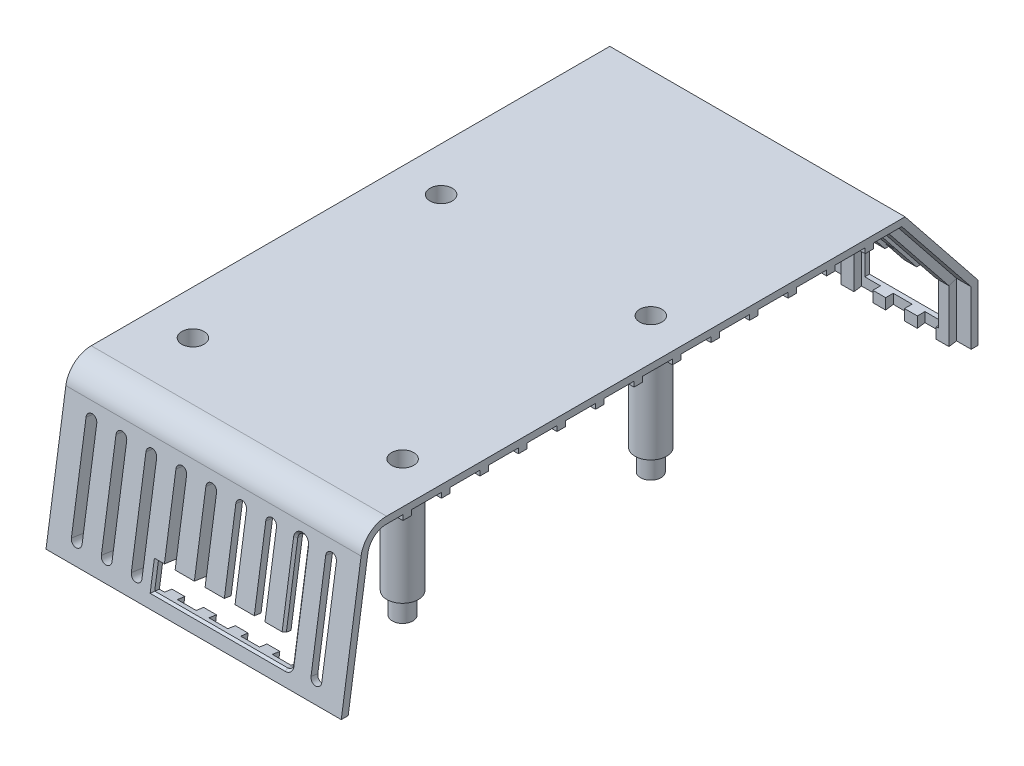
SolidWorks part; units mm, degrees
material "PPS"
ref_plane "前视基准面" through (0, 0, 0) normal (0, 0, 1) x (1, 0, 0)
ref_plane "上视基准面" through (0, 0, 0) normal (0, 1, 0) x (1, 0, 0)
ref_plane "右视基准面" through (0, 0, 0) normal (1, 0, 0) x (0, 0, -1)
sketch "草图2" plane through (0, 0, 0) normal (1, 0, 0) x (0, 0, -1)
  line L32 (-2.0016, 4.5) -> (-2.0016, 17.1644)
  line L33 (-2.0016, 17.1644) -> (-18.214, 37.4471)
  line L34 (-18.214, 37.4471) -> (-138.6289, 37.4471)
  line L35 (-142.9799, 33.7021) -> (-147.3763, 4.5)
  line L36 (0, 0) -> (-169.6172, 0) construction
  line L38 (-17.4446, 39.0471) -> (-138.6289, 39.0471)
  line L39 (-144.5621, 33.9403) -> (-148.9943, 4.5)
  line L40 (-0.4016, 4.5) -> (-0.4016, 17.7253)
  line L41 (-0.4016, 17.7253) -> (-17.4446, 39.0471)
  line L42 (-147.3763, 4.5) -> (-148.9943, 4.5) construction
  line L43 (-142.9799, 33.7021) -> (-147.9563, 0.6471) construction
  line L44 (-147.9563, 0.6471) -> (-2.0016, 0.6471) construction
  line L45 (-149.8153, -0.9529) -> (-0.4016, -0.9529) construction
  line L46 (-144.5621, 33.9403) -> (-149.8153, -0.9529) construction
  line L47 (-0.4016, -0.9529) -> (-0.4016, 17.7253) construction
  line L48 (-2.0016, 0.6471) -> (-2.0016, 17.1644) construction
  line L49 (-2.0016, 4.5) -> (-0.4016, 4.5)
  line L50 (-148.9943, 4.5) -> (-149.1976, 3.15)
  line L51 (-149.1976, 3.15) -> (-147.5795, 3.15)
  line L52 (-147.5795, 3.15) -> (-147.3763, 4.5)
  arc A4 (-138.6289, 39.0471) -> (-144.5621, 33.9403) centre (-138.6289, 33.0471) ccw
  arc A5 (-138.6289, 37.4471) -> (-142.9799, 33.7021) centre (-138.6289, 33.0471) ccw
  dimension "D1" = 1.6
  dimension "D3" = 6
  dimension "D2" = 4.5
  dimension "D4" = 3.15
extrude "凸台-拉伸1" add sketch "草图2" along normal blind 69
sketch "草图7" plane through (0, 3.15, 0) normal (0, -1, 0) x (1, 0, 0)
  line L1 (33, 147.58) -> (33, 145.78)
  line L2 (33, 145.78) -> (36, 145.78)
  line L3 (36, 145.78) -> (36, 147.58)
  line L28 (28.6, 145.78) -> (28.6, 147.58)
  line L29 (25.6, 145.78) -> (28.6, 145.78)
  line L30 (25.6, 147.58) -> (25.6, 145.78)
  line L31 (21.2, 145.78) -> (21.2, 147.58)
  line L32 (18.2, 145.78) -> (21.2, 145.78)
  line L33 (18.2, 147.58) -> (18.2, 145.78)
  line L34 (13.8, 145.78) -> (13.8, 147.58)
  line L35 (10.8, 145.78) -> (13.8, 145.78)
  line L36 (10.8, 147.58) -> (10.8, 145.78)
  line L37 (6.4, 145.78) -> (6.4, 147.58)
  line L38 (3.4, 145.78) -> (6.4, 145.78)
  line L39 (3.4, 147.58) -> (3.4, 145.78)
  line L40 (36, 145.78) -> (28.6, 145.78) construction
  line L41 (40.4, 147.58) -> (40.4, 145.78)
  line L42 (43.4, 145.78) -> (43.4, 147.58)
  line L43 (43.4, 147.58) -> (40.4, 147.58)
  line L44 (40.4, 145.78) -> (43.4, 145.78)
  line L45 (47.8, 147.58) -> (47.8, 145.78)
  line L46 (50.8, 145.78) -> (50.8, 147.58)
  line L47 (50.8, 147.58) -> (47.8, 147.58)
  line L48 (47.8, 145.78) -> (50.8, 145.78)
  line L49 (55.2, 147.58) -> (55.2, 145.78)
  line L50 (58.2, 145.78) -> (58.2, 147.58)
  line L51 (58.2, 147.58) -> (55.2, 147.58)
  line L52 (55.2, 145.78) -> (58.2, 145.78)
  line L53 (62.6, 147.58) -> (62.6, 145.78)
  line L54 (65.6, 145.78) -> (65.6, 147.58)
  line L55 (65.6, 147.58) -> (62.6, 147.58)
  line L56 (62.6, 145.78) -> (65.6, 145.78)
  line L57 (33, 147.58) -> (40.4, 147.58) construction
  line L58 (0, 147.5795) -> (0, 142.9799) construction
  line L103 (28.6, 147.58) -> (25.6, 147.58)
  line L104 (21.2, 147.58) -> (18.2, 147.58)
  line L105 (13.8, 147.58) -> (10.8, 147.58)
  line L106 (36, 147.58) -> (33, 147.58)
  line L107 (6.4, 147.58) -> (3.4, 147.58)
  dimension "D1" = 3
  dimension "D2" = 33
  dimension "D5" = 7.4
  dimension "D7" = 7.4
  dimension "D3" = 5
  dimension "D4" = 1
  dimension "D6" = 5
sketch "草图17" plane through (0, 0, 0) normal (-1, 0, 0) x (0, 0, 1)
  line L0 (147.5795, 3.15) -> (143.0568, 33.1914)
  line L1 (147.5795, 3.15) -> (142.9799, 33.7021) construction
  line L2 (138.1125, 37.4471) -> (18.214, 37.4471)
  line L3 (138.6289, 37.4471) -> (18.214, 37.4471) construction
  line L4 (149.1976, 3.15) -> (147.5795, 3.15) construction
  line L5 (18.214, 37.4471) -> (2.0016, 17.1644)
  line L6 (2.0016, 17.1644) -> (2.0016, 4.5)
  arc A0 (138.1125, 37.4471) -> (143.0568, 33.1914) centre (138.1125, 32.4471) cw
  dimension "D1" = 5
sweep "扫描1" add profiles "草图7" path "草图17"
sketch "草图18" plane through (0, 37.4471, 0) normal (0, -1, 0) x (1, 0, 0)
  line L0 (69, 0.4016) -> (0, 0.4016) construction
  line L1 (0, 17.4446) -> (0, 138.6289) construction
  circle A0 centre (59.3, 67.1616) radius 3.7
  circle A1 centre (59.3, 125.1616) radius 3.7
  circle A2 centre (10.3, 125.1616) radius 3.7
  circle A3 centre (10.3, 67.1616) radius 3.7
  dimension "D4" = 49
  dimension "D1" = 66.76
  dimension "D2" = 66.76
  dimension "D3" = 10.3
  dimension "D5" = 58
  dimension "D6" = 58
  dimension "D7" = 49
  dimension "D8" = 10.3
extrude "凸台-拉伸2" add sketch "草图18" along normal blind 30
sketch "草图28" plane through (69, 0, 0) normal (1, 0, 0) x (0, 0, -1)
  line L0 (-138.6289, 37.4471) -> (-18.214, 37.4471) construction
  line L1 (-132.7865, 37.4471) -> (-134.7865, 37.4471)
  line L2 (-132.7865, 37.4471) -> (-132.7865, 36.2471)
  line L3 (-132.7865, 36.2471) -> (-134.7865, 36.2471)
  line L4 (-134.7865, 37.4471) -> (-134.7865, 36.2471)
  line L5 (-123.7865, 37.4471) -> (-125.7865, 37.4471)
  line L6 (-123.7865, 37.4471) -> (-123.7865, 36.2471)
  line L7 (-123.7865, 36.2471) -> (-125.7865, 36.2471)
  line L8 (-125.7865, 37.4471) -> (-125.7865, 36.2471)
  line L9 (-114.7865, 37.4471) -> (-116.7865, 37.4471)
  line L10 (-114.7865, 37.4471) -> (-114.7865, 36.2471)
  line L11 (-114.7865, 36.2471) -> (-116.7865, 36.2471)
  line L12 (-116.7865, 37.4471) -> (-116.7865, 36.2471)
  line L13 (-105.7865, 37.4471) -> (-107.7865, 37.4471)
  line L14 (-105.7865, 37.4471) -> (-105.7865, 36.2471)
  line L15 (-105.7865, 36.2471) -> (-107.7865, 36.2471)
  line L16 (-107.7865, 37.4471) -> (-107.7865, 36.2471)
  line L17 (-96.7865, 37.4471) -> (-98.7865, 37.4471)
  line L18 (-96.7865, 37.4471) -> (-96.7865, 36.2471)
  line L19 (-96.7865, 36.2471) -> (-98.7865, 36.2471)
  line L20 (-98.7865, 37.4471) -> (-98.7865, 36.2471)
  line L21 (-87.7865, 37.4471) -> (-89.7865, 37.4471)
  line L22 (-87.7865, 37.4471) -> (-87.7865, 36.2471)
  line L23 (-87.7865, 36.2471) -> (-89.7865, 36.2471)
  line L24 (-89.7865, 37.4471) -> (-89.7865, 36.2471)
  line L25 (-78.7865, 37.4471) -> (-80.7865, 37.4471)
  line L26 (-78.7865, 37.4471) -> (-78.7865, 36.2471)
  line L27 (-78.7865, 36.2471) -> (-80.7865, 36.2471)
  line L28 (-80.7865, 37.4471) -> (-80.7865, 36.2471)
  line L29 (-69.7865, 37.4471) -> (-71.7865, 37.4471)
  line L30 (-69.7865, 37.4471) -> (-69.7865, 36.2471)
  line L31 (-69.7865, 36.2471) -> (-71.7865, 36.2471)
  line L32 (-71.7865, 37.4471) -> (-71.7865, 36.2471)
  line L33 (-60.7865, 37.4471) -> (-62.7865, 37.4471)
  line L34 (-60.7865, 37.4471) -> (-60.7865, 36.2471)
  line L35 (-60.7865, 36.2471) -> (-62.7865, 36.2471)
  line L36 (-62.7865, 37.4471) -> (-62.7865, 36.2471)
  line L37 (-51.7865, 37.4471) -> (-53.7865, 37.4471)
  line L38 (-51.7865, 37.4471) -> (-51.7865, 36.2471)
  line L39 (-51.7865, 36.2471) -> (-53.7865, 36.2471)
  line L40 (-53.7865, 37.4471) -> (-53.7865, 36.2471)
  line L41 (-42.7865, 37.4471) -> (-44.7865, 37.4471)
  line L42 (-42.7865, 37.4471) -> (-42.7865, 36.2471)
  line L43 (-42.7865, 36.2471) -> (-44.7865, 36.2471)
  line L44 (-44.7865, 37.4471) -> (-44.7865, 36.2471)
  line L45 (-33.7865, 37.4471) -> (-35.7865, 37.4471)
  line L46 (-33.7865, 37.4471) -> (-33.7865, 36.2471)
  line L47 (-33.7865, 36.2471) -> (-35.7865, 36.2471)
  line L48 (-35.7865, 37.4471) -> (-35.7865, 36.2471)
  line L49 (-24.7865, 37.4471) -> (-26.7865, 37.4471)
  line L50 (-24.7865, 37.4471) -> (-24.7865, 36.2471)
  line L51 (-24.7865, 36.2471) -> (-26.7865, 36.2471)
  line L52 (-26.7865, 37.4471) -> (-26.7865, 36.2471)
  dimension "D1" = 2
  dimension "D2" = 1.2
  dimension "D3" = 13
extrude "凸台-拉伸3" add sketch "草图28" against normal up to surface (69 mm away)
sketch "草图27" plane through (0, 39.0471, 0) normal (0, 1, 0) x (1, 0, 0)
  circle A0 centre (10.3, -67.1616) radius 2.6
  circle A1 centre (59.3, -125.1616) radius 2.6
  circle A2 centre (10.3, -125.1616) radius 2.6
  circle A3 centre (59.3, -67.1616) radius 2.6
extrude "切除-拉伸6" cut sketch "草图27" against normal blind 25
sketch "草图29" plane through (0, 7.4471, 0) normal (0, -1, 0) x (1, 0, 0)
  circle A0 centre (59.3, 67.1616) radius 1.35
  circle A1 centre (10.3, 67.1616) radius 1.35
  circle A2 centre (10.3, 125.1616) radius 1.35
  circle A3 centre (59.3, 125.1616) radius 1.35
extrude "切除-拉伸7" cut sketch "草图29" against normal up to next
sketch "草图30" plane through (0, 7.4471, 0) normal (0, -1, 0) x (1, 0, 0)
  circle A0 centre (59.3, 67.1616) radius 2.4
  circle A1 centre (59.3, 67.1616) radius 4
  circle A2 centre (10.3, 67.1616) radius 2.4
  circle A3 centre (10.3, 67.1616) radius 4
  circle A4 centre (10.3, 125.1616) radius 2.4
  circle A5 centre (10.3, 125.1616) radius 4
  circle A6 centre (59.3, 125.1616) radius 2.4
  circle A7 centre (59.3, 125.1616) radius 4
extrude "切除-拉伸8" cut sketch "草图30" against normal blind 5
sketch "草图31" plane through (0, 6.7142, -8.3998) normal (0, 0.6244, -0.7811) x (-1, 0, 0)
  text T0 "<b>X M U</b>" font "Century Gothic" height 12
extrude "切除-拉伸9" cut sketch "草图31" against normal up to next
sketch "草图32" plane through (0, 22.0337, 146.3546) normal (0, 0.1489, 0.9889) x (1, 0, 0)
  line L0 (34.5, 8.5) -> (34.5, -14.5) construction
  line L1 (35.75, 8.5) -> (35.75, -14.5)
  line L2 (33.25, 8.5) -> (33.25, -14.5)
  line L3 (41.5, 8.5) -> (41.5, -14.5) construction
  line L4 (42.75, 8.5) -> (42.75, -14.5)
  line L5 (40.25, 8.5) -> (40.25, -14.5)
  line L6 (48.5, 8.5) -> (48.5, -14.5) construction
  line L7 (49.75, 8.5) -> (49.75, -14.5)
  line L8 (47.25, 8.5) -> (47.25, -14.5)
  line L9 (55.5, 8.5) -> (55.5, -14.5) construction
  line L10 (56.75, 8.5) -> (56.75, -14.5)
  line L11 (54.25, 8.5) -> (54.25, -14.5)
  line L12 (62.5, 8.5) -> (62.5, -14.5) construction
  line L13 (63.75, 8.5) -> (63.75, -14.5)
  line L14 (61.25, 8.5) -> (61.25, -14.5)
  line L15 (27.5, 8.5) -> (27.5, -14.5) construction
  line L16 (28.75, 8.5) -> (28.75, -14.5)
  line L17 (26.25, 8.5) -> (26.25, -14.5)
  line L18 (20.5, 8.5) -> (20.5, -14.5) construction
  line L19 (21.75, 8.5) -> (21.75, -14.5)
  line L20 (19.25, 8.5) -> (19.25, -14.5)
  line L21 (13.5, 8.5) -> (13.5, -14.5) construction
  line L22 (14.75, 8.5) -> (14.75, -14.5)
  line L23 (12.25, 8.5) -> (12.25, -14.5)
  line L24 (6.5, 8.5) -> (6.5, -14.5) construction
  line L25 (7.75, 8.5) -> (7.75, -14.5)
  line L26 (5.25, 8.5) -> (5.25, -14.5)
  arc A0 (35.75, 8.5) -> (33.25, 8.5) centre (34.5, 8.5) ccw
  arc A1 (33.25, -14.5) -> (35.75, -14.5) centre (34.5, -14.5) ccw
  arc A2 (42.75, 8.5) -> (40.25, 8.5) centre (41.5, 8.5) ccw
  arc A3 (40.25, -14.5) -> (42.75, -14.5) centre (41.5, -14.5) ccw
  arc A4 (49.75, 8.5) -> (47.25, 8.5) centre (48.5, 8.5) ccw
  arc A5 (47.25, -14.5) -> (49.75, -14.5) centre (48.5, -14.5) ccw
  arc A6 (56.75, 8.5) -> (54.25, 8.5) centre (55.5, 8.5) ccw
  arc A7 (54.25, -14.5) -> (56.75, -14.5) centre (55.5, -14.5) ccw
  arc A8 (63.75, 8.5) -> (61.25, 8.5) centre (62.5, 8.5) ccw
  arc A9 (61.25, -14.5) -> (63.75, -14.5) centre (62.5, -14.5) ccw
  arc A10 (28.75, 8.5) -> (26.25, 8.5) centre (27.5, 8.5) ccw
  arc A11 (26.25, -14.5) -> (28.75, -14.5) centre (27.5, -14.5) ccw
  arc A12 (21.75, 8.5) -> (19.25, 8.5) centre (20.5, 8.5) ccw
  arc A13 (19.25, -14.5) -> (21.75, -14.5) centre (20.5, -14.5) ccw
  arc A14 (14.75, 8.5) -> (12.25, 8.5) centre (13.5, 8.5) ccw
  arc A15 (12.25, -14.5) -> (14.75, -14.5) centre (13.5, -14.5) ccw
  arc A16 (7.75, 8.5) -> (5.25, 8.5) centre (6.5, 8.5) ccw
  arc A17 (5.25, -14.5) -> (7.75, -14.5) centre (6.5, -14.5) ccw
  point P2 (34.5, -3)
  point P10 (41.5, -3)
  point P18 (48.5, -3)
  point P25 (55.5, -3)
  point P32 (62.5, -3)
  point P39 (27.5, -3)
  point P46 (20.5, -3)
  point P53 (13.5, -3)
  point P60 (6.5, -3)
  dimension "D1" = 5
  dimension "D3" = 4.5
  dimension "D4" = 4.5
  dimension "D2" = 5
extrude "切除-拉伸10" cut sketch "草图32" against normal up to next
sketch "草图33" plane through (0, 22.0337, 146.3546) normal (0, 0.1489, 0.9889) x (1, 0, 0)
  line L0 (24.4142, -15.75) -> (55.5, -15.75)
  line L1 (55.5, -15.75) -> (55.5, -9.55)
  line L2 (55.5, -9.55) -> (24.4142, -9.55)
  line L3 (24.4142, -9.55) -> (24.4142, -15.75)
  arc A3 (54.25, -14.5) -> (56.75, -14.5) centre (55.5, -14.5) ccw construction
extrude "切除-拉伸11" cut sketch "草图33" against normal up to next
sketch "草图34" plane through (0, 0, 0.4016) normal (0, 0, -1) x (-1, 0, 0)
  line L0 (-63.15, 6.75) -> (-63.15, 16.75)
  line L1 (-63.15, 16.75) -> (-44.15, 16.75)
  line L2 (-44.15, 16.75) -> (-44.15, 6.75)
  line L3 (-44.15, 6.75) -> (-63.15, 6.75)
  line L4 (-69, 4.5) -> (0, 4.5) construction
  dimension "D1" = 2.25
  dimension "D2" = 19
  dimension "D3" = 10
  dimension "D4" = 44.15
extrude "切除-拉伸12" cut sketch "草图34" against normal up to next
chamfer "倒角1" distance 0.5 angle 45 10 edges at (44.15, 11.75, 0.4016) (53.65, 6.75, 0.4016) (53.65, 16.75, 0.4016) (63.15, 11.75, 0.4016) (54.25, 21.5145, 146.4328) (55.5, 31.675, 144.9031) (56.75, 19.0671, 146.8012) (56.3839, 6.8212, 148.6449) (24.4142, 9.5246, 148.2379) (39.9571, 6.4592, 148.6994)
